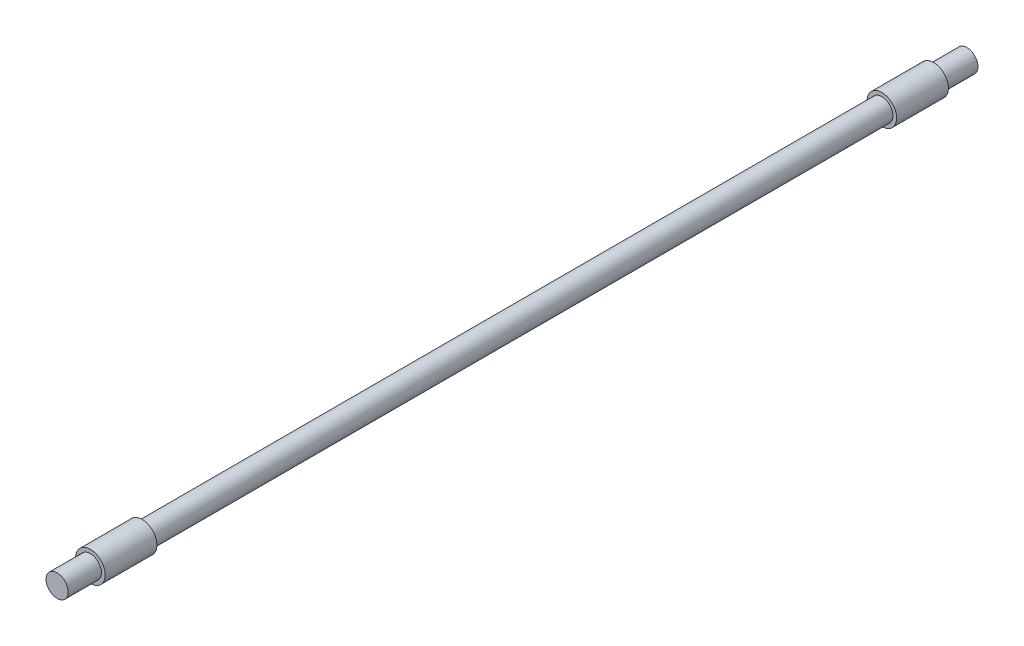
SolidWorks part; units mm, degrees
ref_plane "Front" through (0, 0, 0) normal (0, 0, 1) x (1, 0, 0)
ref_plane "Top" through (0, 0, 0) normal (0, 1, 0) x (1, 0, 0)
ref_plane "Right" through (0, 0, 0) normal (1, 0, 0) x (0, 0, -1)
sketch "Sketch1" plane through (0, 0, 0) normal (0, 0, 1) x (1, 0, 0)
  circle A0 centre (0, 0) radius 15
  dimension "D1" = 30
extrude "Boss-Extrude1" add sketch "Sketch1" along normal blind 1000
sketch "Sketch2" plane through (0, 0, 1000) normal (0, 0, 1) x (1, 0, 0)
  circle A0 centre (0, 0) radius 20
extrude "Boss-Extrude2" add sketch "Sketch2" along normal blind 70
sketch "Sketch3" plane through (0, 0, 1070) normal (0, 0, 1) x (1, 0, 0)
  circle A0 centre (0, 0) radius 15
extrude "Boss-Extrude3" add sketch "Sketch3" along normal blind 45
sketch "Sketch4" plane through (0, 0, 0) normal (0, 0, -1) x (-1, 0, 0)
  circle A0 centre (0, 0) radius 20 construction
  circle A1 centre (0, 0) radius 20
extrude "Boss-Extrude4" add sketch "Sketch4" along normal blind 70
sketch "Sketch5" plane through (0, 0, -70) normal (0, 0, -1) x (-1, 0, 0)
  circle A0 centre (0, 0) radius 15 construction
  circle A1 centre (0, 0) radius 15
extrude "Boss-Extrude5" add sketch "Sketch5" along normal blind 45
